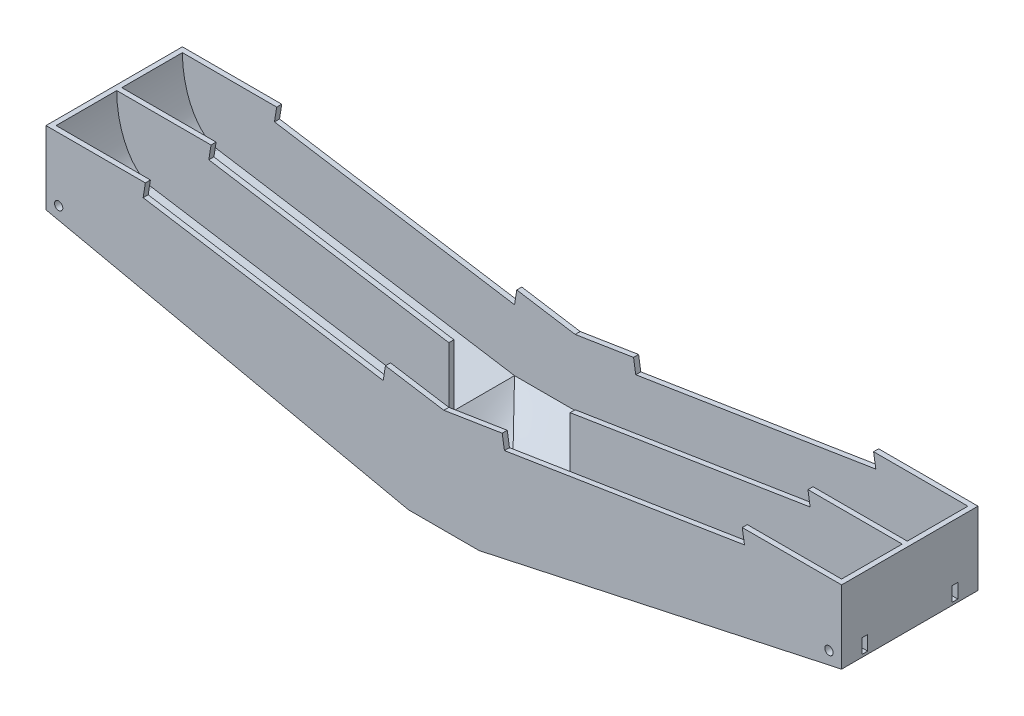
SolidWorks part; units mm, degrees
ref_plane "Front Plane" through (0, 0, 0) normal (0, 0, 1) x (1, 0, 0)
ref_plane "Top Plane" through (0, 0, 0) normal (0, 1, 0) x (1, 0, 0)
ref_plane "Right Plane" through (0, 0, 0) normal (1, 0, 0) x (0, 0, -1)
sketch "Sketch1" plane through (0, 0, 0) normal (0, 1, 0) x (1, 0, 0)
  line L1 (-157.5, -27) -> (157.5, -27)
  line L2 (-157.5, -27) -> (-157.5, 27)
  line L3 (-157.5, 27) -> (157.5, 27)
  line L4 (157.5, -27) -> (157.5, 27)
  line L5 (-157.5, -27) -> (157.5, 27) construction
  line L6 (-157.5, 27) -> (157.5, -27) construction
  point P0 (0, 0)
  dimension "D2" = 315
  dimension "D1" = 54
extrude "Boss-Extrude2" add sketch "Sketch1" along normal blind 60
sketch "Sketch7" plane through (0, 0, 0) normal (0, 0, 1) x (1, 0, 0)
  line L0 (-155.5, 60) -> (-155.5, 36) construction
  line L1 (-141.5, 33.7643) -> (-24, 15)
  line L2 (-157.5, 60) -> (157.5, 60) construction
  line L3 (141.5, 33.7643) -> (24, 15)
  line L4 (-155.5, 36) -> (0, 11.1673) construction
  line L5 (0, 11.1673) -> (155.5, 36) construction
  line L6 (155.5, 36) -> (155.5, 60) construction
  line L7 (155.5, 60) -> (-155.5, 60)
  line L8 (-157.5, 60) -> (-157.5, 0) construction
  line L9 (157.5, 60) -> (157.5, 0) construction
  line L10 (0, 60) -> (0, 0) construction
  line L12 (-24, 15) -> (24, 15)
  line L13 (-157.5, 0) -> (157.5, 0) construction
  ellipse E0 centre (-140.0618, 60) end of major axis (-140.0618, 33.6497) minor radius 15.4382 (-141.5, 33.7643) -> (-155.5, 60) cw
  ellipse E1 centre (140.0618, 60) end of major axis (140.0618, 86.3503) minor radius 15.4382 (155.5, 60) -> (141.5, 33.7643) cw
  point P20 (-131.4011, 31.6326)
  dimension "D1" = 2
  dimension "D2" = 2
  dimension "D3" = 24
  dimension "D4" = 15
  dimension "D5" = 48
  dimension "D6" = 16
extrude "Cut-Extrude2" cut sketch "Sketch7" along normal offset from surface 2 and the other way offset from surface 2 up to face at (0, 30, 27) other way up to face at (0, 30, -27)
extrude "Boss-Extrude3" add sketch "Sketch7<2>" along normal mid plane 2
sketch "Sketch7<2>" plane through (0, 0, 0) normal (0, 0, 1) x (1, 0, 0) same geometry as "Sketch7"
sketch "Sketch9" plane through (0, 15, 0) normal (0, 1, 0) x (1, 0, 0)
  line L1 (-24, -25) -> (24, -25)
  line L2 (-24, -25) -> (-24, 25)
  line L3 (-24, 25) -> (24, 25)
  line L4 (24, -25) -> (24, 25)
  line L5 (-24, -25) -> (24, 25) construction
  line L6 (-24, 25) -> (24, -25) construction
  point P0 (0, 0)
extrude "Cut-Extrude5" cut sketch "Sketch9" along normal through all
sketch "Sketch10" plane through (0, 0, 0) normal (0, -1, 0) x (1, 0, 0)
  circle A0 centre (0, 0) radius 12
  dimension "D1" = 24
extrude "Cut-Extrude6" cut sketch "Sketch10" against normal blind 2
sketch "Sketch4" plane through (0, 2, 0) normal (0, -1, 0) x (1, 0, 0)
  circle A0 centre (0, 0) radius 12
  dimension "D1" = 24
loft "Cut-Loft3" cut profiles "Sketch4", "Sketch9<2>" connector at (0, 2, -12) connector at (-24, 15, -25)
sketch "Sketch9<2>" plane through (0, 15, 0) normal (0, 1, 0) x (1, 0, 0) same geometry as "Sketch9"
sketch "Sketch11" plane through (0, 0, 27) normal (0, 0, 1) x (1, 0, 0)
  line L0 (-157.5, 31.0917) -> (-14, 0)
  line L1 (-157.5, 60) -> (-157.5, 0) construction
  line L2 (-157.5, 0) -> (157.5, 0) construction
  line L3 (-14, 0) -> (-157.5, 0)
  line L4 (-157.5, 0) -> (-157.5, 31.0917)
  line L5 (157.5, 31.0917) -> (157.5, 0)
  line L6 (157.5, 60) -> (157.5, 0) construction
  line L7 (157.5, 0) -> (14, 0)
  line L8 (14, 0) -> (157.5, 31.0917)
  line L9 (-118.1608, 60) -> (-119.042, 54.4819)
  line L10 (-24, 60) -> (-155.5, 60) construction
  line L11 (-119.042, 54.4819) -> (-24, 39.3041)
  line L12 (-118.1608, 60) -> (118.1608, 60)
  line L13 (155.5, 60) -> (24, 60) construction
  line L14 (-141.5, 33.7643) -> (-24, 15) construction
  line L15 (0, 60) -> (0, 0) construction
  line L16 (-141.5, 33.7643) -> (-24, 15) construction
  line L17 (118.1608, 60) -> (119.042, 54.4819)
  line L18 (119.042, 54.4819) -> (24, 39.3041)
  line L19 (-24, 39.3041) -> (-23.1188, 44.8222)
  line L20 (-23.1188, 44.8222) -> (0, 41.1302)
  line L21 (0, 41.1302) -> (23.1188, 44.8222)
  line L22 (23.1188, 44.8222) -> (24, 39.3041)
  line L23 (-24, 60) -> (-24, 15) construction
  line L24 (-12, 0) -> (12, 0) construction
  line L25 (-12, 0) -> (12, 0) construction
  line L26 (-141.5, 33.7643) -> (-142.7705, 27.9003) construction
  line L27 (-152.5, 35) -> (152.5, 35) construction
  line L28 (-157.5, 60) -> (-157.5, 0) construction
  circle A0 centre (-152.5, 35) radius 1.65
  circle A1 centre (152.5, 35) radius 1.65
  point P33 (-154.15, 35)
  point P42 (0, 0)
  point P45 (0, 35)
  dimension "D5" = 3.3
  dimension "D1" = 6
  dimension "D2" = 2
  dimension "D3" = 24
  dimension "D4" = 5.588
  dimension "D6" = 25
  dimension "D7" = 5
extrude "Cut-Extrude7" cut sketch "Sketch11" against normal through all
ref_plane "Plane1" through (0, 0, 19) normal (0, 0, 1) x (1, 0, 0)
sketch "Sketch12" plane through (0, 0, 19) normal (0, 0, 1) x (1, 0, 0)
  line L0 (-157.5, 60) -> (-157.5, 31.0917) construction
  line L1 (-150.8546, 37.85) -> (-157.5, 37.85)
  line L2 (-157.5, 37.85) -> (-157.5, 32.15)
  line L3 (157.5, 37.85) -> (157.5, 32.15)
  line L4 (-157.5, 32.15) -> (-150.8546, 32.15)
  line L5 (-150.8546, 32.15) -> (-149.2091, 35)
  line L6 (-149.2091, 35) -> (-150.8546, 37.85)
  line L7 (150.8546, 37.85) -> (149.2091, 35)
  line L8 (149.2091, 35) -> (150.8546, 32.15)
  line L9 (150.8546, 32.15) -> (157.5, 32.15)
  line L10 (157.5, 60) -> (157.5, 31.0917) construction
  line L12 (157.5, 37.85) -> (150.8546, 37.85)
  line L13 (-153.7857, 38.4731) -> (-155.104, 36.1897) [skipped]
  line L14 (-156.1507, 35.6231) -> (-154.8323, 33.3397) [skipped]
  line L15 (156.3932, 33.9568) -> (154.9682, 36.425) [skipped]
  line L16 (154.1454, 32.15) -> (154.9682, 33.575) [skipped]
  circle A0 centre (-152.5, 35) radius 2.85 construction
  circle A1 centre (152.5, 35) radius 2.85 construction
  point P4 (157.3067, 32.15)
  point P14 (157.2788, 37.85)
  dimension "D1" = 5.7
extrude "Cut-Extrude8" cut sketch "Sketch12" against normal blind 2.3
ref_plane "Plane2" through (0, 0, -19) normal (0, 0, -1) x (-1, 0, 0)
sketch "Sketch13" plane through (0, 0, -19) normal (0, 0, -1) x (-1, 0, 0)
  line L1 (-150.8546, 37.85) -> (-157.5, 37.85)
  line L2 (-157.5, 37.85) -> (-157.5, 32.15)
  line L3 (157.5, 37.85) -> (157.5, 32.15)
  line L4 (-157.5, 32.15) -> (-150.8546, 32.15)
  line L5 (-150.8546, 32.15) -> (-149.2091, 35)
  line L6 (-149.2091, 35) -> (-150.8546, 37.85)
  line L7 (150.8546, 37.85) -> (149.2091, 35)
  line L8 (149.2091, 35) -> (150.8546, 32.15)
  line L9 (150.8546, 32.15) -> (157.5, 32.15)
  line L11 (157.5, 60) -> (157.5, 31.0917) construction
  line L12 (157.5, 37.85) -> (150.8546, 37.85)
  line L13 (-153.7857, 38.4731) -> (-155.104, 36.1897) [skipped]
  line L14 (-156.1507, 35.6231) -> (-154.8323, 33.3397) [skipped]
  line L15 (156.3932, 33.9568) -> (154.9682, 36.425) [skipped]
  line L16 (154.1454, 32.15) -> (154.9682, 33.575) [skipped]
  line L17 (-157.5, 60) -> (-157.5, 31.0917) construction
  circle A0 centre (-152.5, 35) radius 2.85 construction
  circle A1 centre (152.5, 35) radius 2.85 construction
  circle A3 centre (-152.5, 35) radius 1.65 construction
  circle A4 centre (-152.5, 35) radius 1.65 construction
  circle A5 centre (152.5, 35) radius 1.65 construction
  circle A6 centre (152.5, 35) radius 1.65 construction
  point P0 (-156.7894, 37.85)
  point P4 (157.3067, 32.15)
  point P14 (157.2788, 37.85)
  point P16 (-152.0993, 34.5506)
  point P23 (-152.4701, 35.0804)
  point P24 (-151.9933, 34.4446)
  point P26 (-152.4966, 34.9745)
  point P33 (-152.3377, 35)
  dimension "D1" = 5.7
extrude "Cut-Extrude9" cut sketch "Sketch13" against normal blind 2.3
